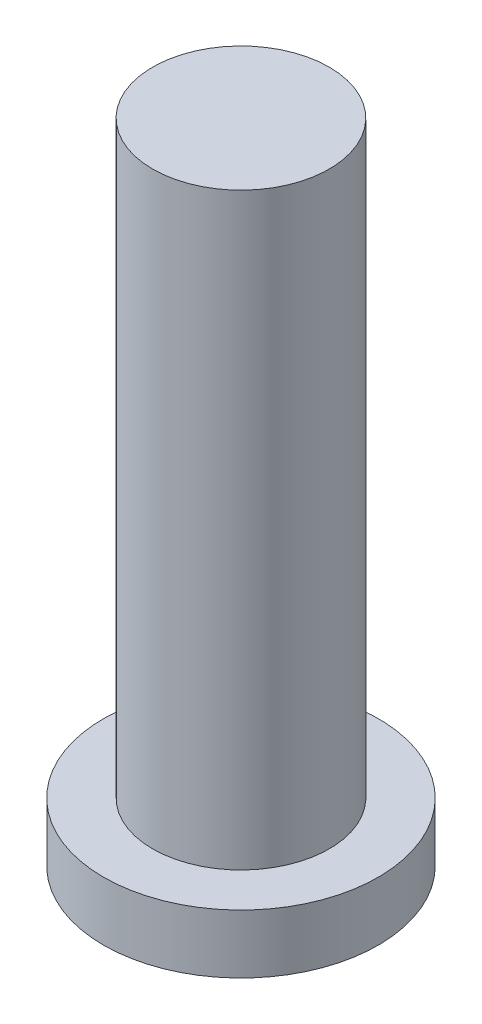
SolidWorks part; units mm, degrees
ref_plane "Front Plane" through (0, 0, 0) normal (0, 0, 1) x (1, 0, 0)
ref_plane "Top Plane" through (0, 0, 0) normal (0, 1, 0) x (1, 0, 0)
ref_plane "Right Plane" through (0, 0, 0) normal (1, 0, 0) x (0, 0, -1)
sketch "Sketch1" plane through (0, 0, 0) normal (0, 1, 0) x (1, 0, 0)
  circle A0 centre (0, 0) radius 14
  circle A1 centre (0, 0) radius 9
  dimension "D1" = 18
  dimension "D2" = 28
extrude "Boss-Extrude2" add sketch "Sketch1" along normal blind 60 contours A1
extrude "Boss-Extrude3" add sketch "Sketch1<3>" against normal blind 6 contours A0
sketch "Sketch1<3>" plane through (0, 0, 0) normal (0, 1, 0) x (1, 0, 0) same geometry as "Sketch1"
equation "\"handleTurnShaft\"= \"shaftDiam\" - 2 * \"clearance\""
equation "\"handleTurnShaftFlange\"= \"shaftDiam\" * 1.4"
equation "\"handleTurnLen\"= \"handleShaftLen\""
equation "\"handleTurnFlangeLen\"= \"handleShaftLen\" / 10"
equation "\"shaftDiam\" = 20mm"
equation "\"keyW\" = 8mm"
equation "\"keyL\" = 10mm"
equation "\"clearance\" = 1mm"
equation "\"handleShaftLen\" = 60mm"
equation "\"D2@Sketch1\"=\"handleTurnShaftFlange\""
equation "\"D1@Sketch1\"=\"handleTurnShaft\""
equation "\"D1@Boss-Extrude2\"=\"handleTurnLen\""
equation "\"D1@Boss-Extrude3\"=\"handleTurnFlangeLen\""
